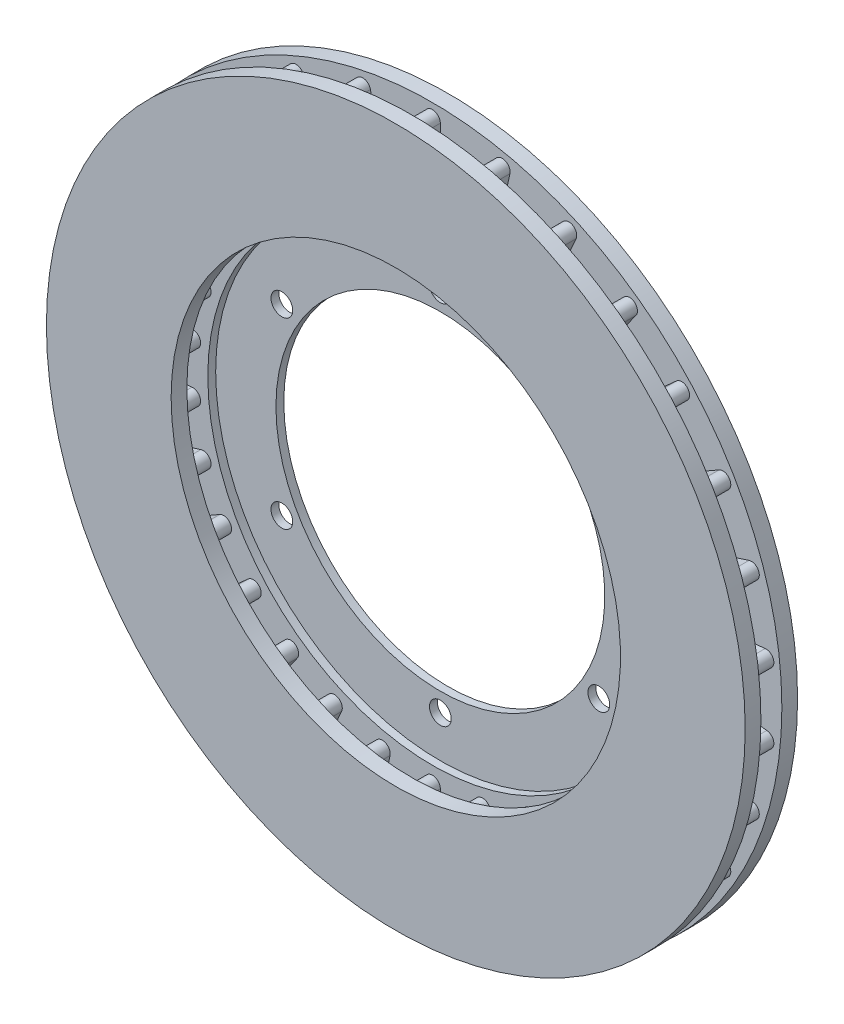
SolidWorks part; units mm, degrees
material "Gray Cast Iron"
ref_plane "Front Plane" through (0, 0, 0) normal (0, 0, 1) x (1, 0, 0)
ref_plane "Top Plane" through (0, 0, 0) normal (0, 1, 0) x (1, 0, 0)
ref_plane "Right Plane" through (0, 0, 0) normal (1, 0, 0) x (0, 0, -1)
sketch "Sketch1" plane through (0, 0, 0) normal (0, 0, 1) x (1, 0, 0)
  circle A0 centre (0, 0) radius 133.35
  circle A1 centre (0, 0) radius 69.85 construction
  circle A2 centre (0, 0) radius 85.75
  dimension "D1" = 266.7
  dimension "D2" = 139.7
  dimension "D3" = 171.5
extrude "Extrude1" add sketch "Sketch1" along normal blind 20
sketch "Sketch2" plane through (0, 0, 0) normal (0, 0, 1) x (1, 0, 0)
  circle A0 centre (0, 0) radius 85.75
  circle A1 centre (0, 0) radius 62.75
  dimension "D1" = 125.5
extrude "Extrude2" add sketch "Sketch2" along normal blind 3
sketch "Sketch3" plane through (0, 0, 0) normal (0, 0, 1) x (1, 0, 0)
  circle A0 centre (0, 69.85) radius 4.15
  circle A1 centre (60.4919, 34.925) radius 4.15
  circle A2 centre (60.4919, -34.925) radius 4.15
  circle A3 centre (0, -69.85) radius 4.15
  circle A4 centre (-60.4919, -34.925) radius 4.15
  circle A5 centre (-60.4919, 34.925) radius 4.15
  dimension "D1" = 8.3
  dimension "D2" = 69.85
extrude "Extrude7" cut sketch "Sketch3" along normal blind 11
sketch "Sketch4" plane through (0, 0, 0) normal (1, 0, 0) x (0, 0, -1)
  line L0 (-33.9382, 0) -> (14.3406, 0) construction
sketch3d "3DSketch1" [suppressed]
  line L0 (0, 69.85, 3) -> (0, 69.85, 0) construction
  line L1 (0, 69.85, 3) -> (0, 69.85, 0) construction
  line L2 (-60.4919, 34.925, 3) -> (-60.4919, 34.925, 0) construction
  line L3 (-60.4919, 34.925, 3) -> (-60.4919, 34.925, 0) construction
  line L4 (-60.4919, -34.925, 3) -> (-60.4919, -34.925, 0) construction
  line L5 (-60.4919, -34.925, 3) -> (-60.4919, -34.925, 0) construction
  line L6 (0, -69.85, 3) -> (0, -69.85, 0) construction
  line L7 (0, -69.85, 3) -> (0, -69.85, 0) construction
  line L8 (60.4919, -34.925, 3) -> (60.4919, -34.925, 0) construction
  line L9 (60.4919, -34.925, 3) -> (60.4919, -34.925, 0) construction
  line L10 (60.4919, 34.925, 3) -> (60.4919, 34.925, 0) construction
  line L11 (60.4919, 34.925, 3) -> (60.4919, 34.925, 0) construction
ref_plane "PlaneDiscCenter" through (0, 0, 10) normal (0, 0, 1) x (1, 0, 0)
sketch "Sketch5" plane through (0, 0, 10) normal (0, 0, 1) x (1, 0, 0)
  line L0 (0, 128) -> (0, 92) construction
  line L1 (3, 128) -> (3, 92)
  line L2 (-3, 128) -> (-3, 92)
  line L3 (26.6127, 125.2029) -> (19.1279, 89.9896) construction
  line L4 (29.5471, 124.5792) -> (22.0623, 89.3658)
  line L5 (23.6783, 125.8266) -> (16.1934, 90.6133)
  line L6 (52.0623, 116.9338) -> (37.4198, 84.0462) construction
  line L7 (54.8029, 115.7136) -> (40.1604, 82.826)
  line L8 (49.3217, 118.154) -> (34.6791, 85.2664)
  line L9 (75.2365, 103.5542) -> (54.0762, 74.4296) construction
  line L10 (77.6636, 101.7908) -> (56.5033, 72.6662)
  line L11 (72.8095, 105.3175) -> (51.6492, 76.1929)
  line L12 (95.1225, 85.6487) -> (68.3693, 61.56) construction
  line L13 (97.1299, 83.4193) -> (70.3767, 59.3306)
  line L14 (93.1151, 87.8782) -> (66.3619, 63.7895)
  line L15 (110.8513, 64) -> (79.6743, 46) construction
  line L16 (112.3513, 61.4019) -> (81.1743, 43.4019)
  line L17 (109.3513, 66.5981) -> (78.1743, 48.5981)
  line L18 (121.7352, 39.5542) -> (87.4972, 28.4296) construction
  line L19 (122.6623, 36.701) -> (88.4243, 25.5764)
  line L20 (120.8082, 42.4073) -> (86.5701, 31.2827)
  line L21 (127.2988, 13.3796) -> (91.496, 9.6166) construction
  line L22 (127.6124, 10.3961) -> (91.8096, 6.6331)
  line L23 (126.9852, 16.3632) -> (91.1824, 12.6002)
  line L24 (127.2988, -13.3796) -> (91.496, -9.6166) construction
  line L25 (126.9852, -16.3632) -> (91.1824, -12.6002)
  line L26 (127.6124, -10.3961) -> (91.8096, -6.6331)
  line L27 (121.7352, -39.5542) -> (87.4972, -28.4296) construction
  line L28 (120.8082, -42.4073) -> (86.5701, -31.2827)
  line L29 (122.6623, -36.701) -> (88.4243, -25.5764)
  line L30 (110.8513, -64) -> (79.6743, -46) construction
  line L31 (109.3513, -66.5981) -> (78.1743, -48.5981)
  line L32 (112.3513, -61.4019) -> (81.1743, -43.4019)
  line L33 (95.1225, -85.6487) -> (68.3693, -61.56) construction
  line L34 (93.1151, -87.8782) -> (66.3619, -63.7895)
  line L35 (97.1299, -83.4193) -> (70.3767, -59.3306)
  line L36 (75.2365, -103.5542) -> (54.0762, -74.4296) construction
  line L37 (72.8095, -105.3175) -> (51.6492, -76.1929)
  line L38 (77.6636, -101.7908) -> (56.5033, -72.6662)
  line L39 (52.0623, -116.9338) -> (37.4198, -84.0462) construction
  line L40 (49.3217, -118.154) -> (34.6791, -85.2664)
  line L41 (54.8029, -115.7136) -> (40.1604, -82.826)
  line L42 (26.6127, -125.2029) -> (19.1279, -89.9896) construction
  line L43 (23.6783, -125.8266) -> (16.1934, -90.6133)
  line L44 (29.5471, -124.5792) -> (22.0623, -89.3658)
  line L45 (0, -128) -> (0, -92) construction
  line L46 (-3, -128) -> (-3, -92)
  line L47 (3, -128) -> (3, -92)
  line L48 (-26.6127, -125.2029) -> (-19.1279, -89.9896) construction
  line L49 (-29.5471, -124.5792) -> (-22.0623, -89.3658)
  line L50 (-23.6783, -125.8266) -> (-16.1934, -90.6133)
  line L51 (-52.0623, -116.9338) -> (-37.4198, -84.0462) construction
  line L52 (-54.8029, -115.7136) -> (-40.1604, -82.826)
  line L53 (-49.3217, -118.154) -> (-34.6791, -85.2664)
  line L54 (-75.2365, -103.5542) -> (-54.0762, -74.4296) construction
  line L55 (-77.6636, -101.7908) -> (-56.5033, -72.6662)
  line L56 (-72.8095, -105.3175) -> (-51.6492, -76.1929)
  line L57 (-95.1225, -85.6487) -> (-68.3693, -61.56) construction
  line L58 (-97.1299, -83.4193) -> (-70.3767, -59.3306)
  line L59 (-93.1151, -87.8782) -> (-66.3619, -63.7895)
  line L60 (-110.8513, -64) -> (-79.6743, -46) construction
  line L61 (-112.3513, -61.4019) -> (-81.1743, -43.4019)
  line L62 (-109.3513, -66.5981) -> (-78.1743, -48.5981)
  line L63 (-121.7352, -39.5542) -> (-87.4972, -28.4296) construction
  line L64 (-122.6623, -36.701) -> (-88.4243, -25.5764)
  line L65 (-120.8082, -42.4073) -> (-86.5701, -31.2827)
  line L66 (-127.2988, -13.3796) -> (-91.496, -9.6166) construction
  line L67 (-127.6124, -10.3961) -> (-91.8096, -6.6331)
  line L68 (-126.9852, -16.3632) -> (-91.1824, -12.6002)
  line L69 (-127.2988, 13.3796) -> (-91.496, 9.6166) construction
  line L70 (-126.9852, 16.3632) -> (-91.1824, 12.6002)
  line L71 (-127.6124, 10.3961) -> (-91.8096, 6.6331)
  line L72 (-121.7352, 39.5542) -> (-87.4972, 28.4296) construction
  line L73 (-120.8082, 42.4073) -> (-86.5701, 31.2827)
  line L74 (-122.6623, 36.701) -> (-88.4243, 25.5764)
  line L75 (-110.8513, 64) -> (-79.6743, 46) construction
  line L76 (-109.3513, 66.5981) -> (-78.1743, 48.5981)
  line L77 (-112.3513, 61.4019) -> (-81.1743, 43.4019)
  line L78 (-95.1225, 85.6487) -> (-68.3693, 61.56) construction
  line L79 (-93.1151, 87.8782) -> (-66.3619, 63.7895)
  line L80 (-97.1299, 83.4193) -> (-70.3767, 59.3306)
  line L81 (-75.2365, 103.5542) -> (-54.0762, 74.4296) construction
  line L82 (-72.8095, 105.3175) -> (-51.6492, 76.1929)
  line L83 (-77.6636, 101.7908) -> (-56.5033, 72.6662)
  line L84 (-52.0623, 116.9338) -> (-37.4198, 84.0462) construction
  line L85 (-49.3217, 118.154) -> (-34.6791, 85.2664)
  line L86 (-54.8029, 115.7136) -> (-40.1604, 82.826)
  line L87 (-26.6127, 125.2029) -> (-19.1279, 89.9896) construction
  line L88 (-23.6783, 125.8266) -> (-16.1934, 90.6133)
  line L89 (-29.5471, 124.5792) -> (-22.0623, 89.3658)
  line L90 (0, 0) -> (0, 128) construction
  arc A0 (3, 128) -> (-3, 128) centre (0, 128) ccw
  arc A1 (-3, 92) -> (3, 92) centre (0, 92) ccw
  arc A2 (29.5471, 124.5792) -> (23.6783, 125.8266) centre (26.6127, 125.2029) ccw
  arc A3 (16.1934, 90.6133) -> (22.0623, 89.3658) centre (19.1279, 89.9896) ccw
  arc A4 (54.8029, 115.7136) -> (49.3217, 118.154) centre (52.0623, 116.9338) ccw
  arc A5 (34.6791, 85.2664) -> (40.1604, 82.826) centre (37.4198, 84.0462) ccw
  arc A6 (77.6636, 101.7908) -> (72.8095, 105.3175) centre (75.2365, 103.5542) ccw
  arc A7 (51.6492, 76.1929) -> (56.5033, 72.6662) centre (54.0762, 74.4296) ccw
  arc A8 (97.1299, 83.4193) -> (93.1151, 87.8782) centre (95.1225, 85.6487) ccw
  arc A9 (66.3619, 63.7895) -> (70.3767, 59.3306) centre (68.3693, 61.56) ccw
  arc A10 (112.3513, 61.4019) -> (109.3513, 66.5981) centre (110.8513, 64) ccw
  arc A11 (78.1743, 48.5981) -> (81.1743, 43.4019) centre (79.6743, 46) ccw
  arc A12 (122.6623, 36.701) -> (120.8082, 42.4073) centre (121.7352, 39.5542) ccw
  arc A13 (86.5701, 31.2827) -> (88.4243, 25.5764) centre (87.4972, 28.4296) ccw
  arc A14 (127.6124, 10.3961) -> (126.9852, 16.3632) centre (127.2988, 13.3796) ccw
  arc A15 (91.1824, 12.6002) -> (91.8096, 6.6331) centre (91.496, 9.6166) ccw
  arc A16 (126.9852, -16.3632) -> (127.6124, -10.3961) centre (127.2988, -13.3796) ccw
  arc A17 (91.8096, -6.6331) -> (91.1824, -12.6002) centre (91.496, -9.6166) ccw
  arc A18 (120.8082, -42.4073) -> (122.6623, -36.701) centre (121.7352, -39.5542) ccw
  arc A19 (88.4243, -25.5764) -> (86.5701, -31.2827) centre (87.4972, -28.4296) ccw
  arc A20 (109.3513, -66.5981) -> (112.3513, -61.4019) centre (110.8513, -64) ccw
  arc A21 (81.1743, -43.4019) -> (78.1743, -48.5981) centre (79.6743, -46) ccw
  arc A22 (93.1151, -87.8782) -> (97.1299, -83.4193) centre (95.1225, -85.6487) ccw
  arc A23 (70.3767, -59.3306) -> (66.3619, -63.7895) centre (68.3693, -61.56) ccw
  arc A24 (72.8095, -105.3175) -> (77.6636, -101.7908) centre (75.2365, -103.5542) ccw
  arc A25 (56.5033, -72.6662) -> (51.6492, -76.1929) centre (54.0762, -74.4296) ccw
  arc A26 (49.3217, -118.154) -> (54.8029, -115.7136) centre (52.0623, -116.9338) ccw
  arc A27 (40.1604, -82.826) -> (34.6791, -85.2664) centre (37.4198, -84.0462) ccw
  arc A28 (23.6783, -125.8266) -> (29.5471, -124.5792) centre (26.6127, -125.2029) ccw
  arc A29 (22.0623, -89.3658) -> (16.1934, -90.6133) centre (19.1279, -89.9896) ccw
  arc A30 (-3, -128) -> (3, -128) centre (0, -128) ccw
  arc A31 (3, -92) -> (-3, -92) centre (0, -92) ccw
  arc A32 (-29.5471, -124.5792) -> (-23.6783, -125.8266) centre (-26.6127, -125.2029) ccw
  arc A33 (-16.1934, -90.6133) -> (-22.0623, -89.3658) centre (-19.1279, -89.9896) ccw
  arc A34 (-54.8029, -115.7136) -> (-49.3217, -118.154) centre (-52.0623, -116.9338) ccw
  arc A35 (-34.6791, -85.2664) -> (-40.1604, -82.826) centre (-37.4198, -84.0462) ccw
  arc A36 (-77.6636, -101.7908) -> (-72.8095, -105.3175) centre (-75.2365, -103.5542) ccw
  arc A37 (-51.6492, -76.1929) -> (-56.5033, -72.6662) centre (-54.0762, -74.4296) ccw
  arc A38 (-97.1299, -83.4193) -> (-93.1151, -87.8782) centre (-95.1225, -85.6487) ccw
  arc A39 (-66.3619, -63.7895) -> (-70.3767, -59.3306) centre (-68.3693, -61.56) ccw
  arc A40 (-112.3513, -61.4019) -> (-109.3513, -66.5981) centre (-110.8513, -64) ccw
  arc A41 (-78.1743, -48.5981) -> (-81.1743, -43.4019) centre (-79.6743, -46) ccw
  arc A42 (-122.6623, -36.701) -> (-120.8082, -42.4073) centre (-121.7352, -39.5542) ccw
  arc A43 (-86.5701, -31.2827) -> (-88.4243, -25.5764) centre (-87.4972, -28.4296) ccw
  arc A44 (-127.6124, -10.3961) -> (-126.9852, -16.3632) centre (-127.2988, -13.3796) ccw
  arc A45 (-91.1824, -12.6002) -> (-91.8096, -6.6331) centre (-91.496, -9.6166) ccw
  arc A46 (-126.9852, 16.3632) -> (-127.6124, 10.3961) centre (-127.2988, 13.3796) ccw
  arc A47 (-91.8096, 6.6331) -> (-91.1824, 12.6002) centre (-91.496, 9.6166) ccw
  arc A48 (-120.8082, 42.4073) -> (-122.6623, 36.701) centre (-121.7352, 39.5542) ccw
  arc A49 (-88.4243, 25.5764) -> (-86.5701, 31.2827) centre (-87.4972, 28.4296) ccw
  arc A50 (-109.3513, 66.5981) -> (-112.3513, 61.4019) centre (-110.8513, 64) ccw
  arc A51 (-81.1743, 43.4019) -> (-78.1743, 48.5981) centre (-79.6743, 46) ccw
  arc A52 (-93.1151, 87.8782) -> (-97.1299, 83.4193) centre (-95.1225, 85.6487) ccw
  arc A53 (-70.3767, 59.3306) -> (-66.3619, 63.7895) centre (-68.3693, 61.56) ccw
  arc A54 (-72.8095, 105.3175) -> (-77.6636, 101.7908) centre (-75.2365, 103.5542) ccw
  arc A55 (-56.5033, 72.6662) -> (-51.6492, 76.1929) centre (-54.0762, 74.4296) ccw
  arc A56 (-49.3217, 118.154) -> (-54.8029, 115.7136) centre (-52.0623, 116.9338) ccw
  arc A57 (-40.1604, 82.826) -> (-34.6791, 85.2664) centre (-37.4198, 84.0462) ccw
  arc A58 (-23.6783, 125.8266) -> (-29.5471, 124.5792) centre (-26.6127, 125.2029) ccw
  arc A59 (-22.0623, 89.3658) -> (-16.1934, 90.6133) centre (-19.1279, 89.9896) ccw
  point P3 (0, 110)
  point P13 (22.8703, 107.5962)
  point P20 (44.741, 100.49)
  point P27 (64.6564, 88.9919)
  point P34 (81.7459, 73.6044)
  point P41 (95.2628, 55)
  point P48 (104.6162, 33.9919)
  point P55 (109.3974, 11.4981)
  point P62 (109.3974, -11.4981)
  point P69 (104.6162, -33.9919)
  point P76 (95.2628, -55)
  point P83 (81.7459, -73.6044)
  point P90 (64.6564, -88.9919)
  point P97 (44.741, -100.49)
  point P104 (22.8703, -107.5962)
  point P111 (0, -110)
  point P118 (-22.8703, -107.5962)
  point P125 (-44.741, -100.49)
  point P132 (-64.6564, -88.9919)
  point P139 (-81.7459, -73.6044)
  point P146 (-95.2628, -55)
  point P153 (-104.6162, -33.9919)
  point P160 (-109.3974, -11.4981)
  point P167 (-109.3974, 11.4981)
  point P174 (-104.6162, 33.9919)
  point P181 (-95.2628, 55)
  point P188 (-81.7459, 73.6044)
  point P195 (-64.6564, 88.9919)
  point P202 (-44.741, 100.49)
  point P209 (-22.8703, 107.5962)
  dimension "D1" = 6
  dimension "D2" = 110
  dimension "D3" = 36
  dimension "D4" = 30
  dimension "D5" = 128
extrude "Cut-Extrude1" cut sketch "Sketch5" against normal blind 4 and the other way blind 4 flip side to cut
move or copy body "Body-Move/Copy1" [suppressed] bodies to move or copy 104
